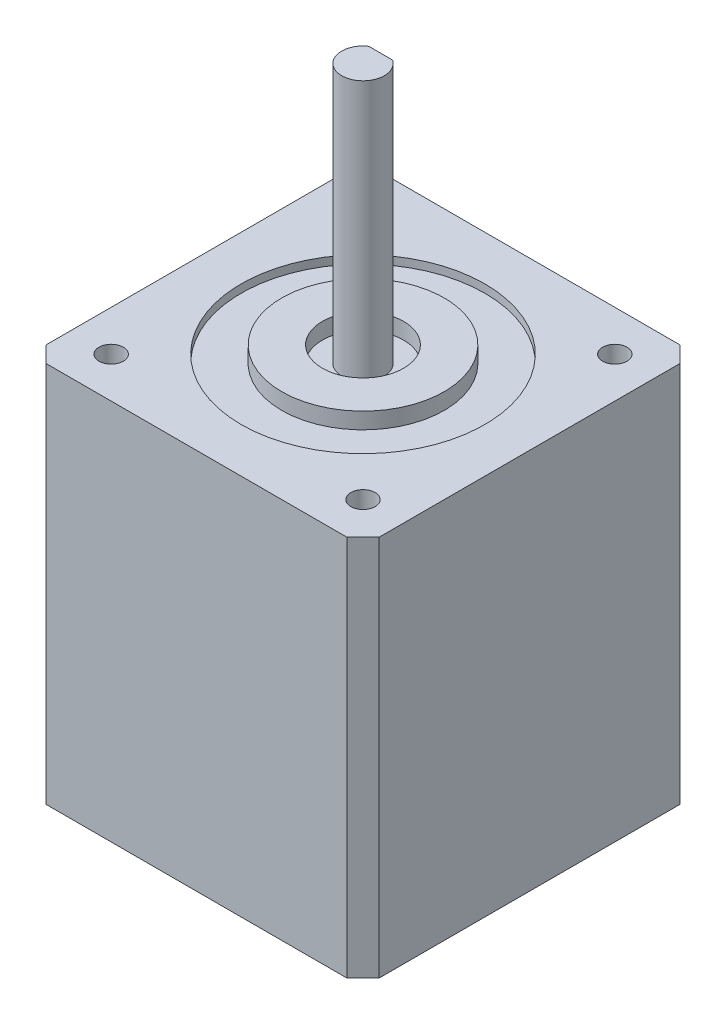
SolidWorks part; units mm, degrees
ref_plane "Front Plane" through (0, 0, 0) normal (0, 0, 1) x (1, 0, 0)
ref_plane "Top Plane" through (0, 0, 0) normal (0, 1, 0) x (1, 0, 0)
ref_plane "Right Plane" through (0, 0, 0) normal (1, 0, 0) x (0, 0, -1)
sketch "Sketch1" plane through (0, 0, 0) normal (0, 1, 0) x (1, 0, 0)
  line L0 (-20.5, 18.5) -> (-18.5, 20.5)
  line L1 (-18.5, -20.5) -> (18.5, -20.5)
  line L2 (-20.5, -18.5) -> (-20.5, 18.5)
  line L3 (-18.5, 20.5) -> (18.5, 20.5)
  line L4 (20.5, -18.5) -> (20.5, 18.5)
  line L5 (-20.5, -20.5) -> (20.5, 20.5) construction
  line L6 (-20.5, 20.5) -> (20.5, -20.5) construction
  line L7 (-18.5, -20.5) -> (-20.5, -18.5)
  line L8 (18.5, -20.5) -> (20.5, -18.5)
  line L9 (20.5, 18.5) -> (18.5, 20.5)
  point P0 (0, 0)
  dimension "D1" = 41
  dimension "D2" = 41
extrude "Boss-Extrude1" add sketch "Sketch1" along normal blind 47
sketch "Sketch2" plane through (0, 47, 0) normal (0, 1, 0) x (-1, 0, 0)
  circle A0 centre (0, 0) radius 15
extrude "Cut-Extrude1" cut sketch "Sketch2" against normal blind 1
sketch "Sketch3" plane through (0, 46, 0) normal (0, 1, 0) x (1, 0, 0)
  circle A0 centre (0, 0) radius 10
  circle A1 centre (0, 0) radius 5
extrude "Boss-Extrude2" add sketch "Sketch3" along normal blind 2
sketch "Sketch4" plane through (0, 46, 0) normal (0, 1, 0) x (1, 0, 0)
  line L0 (-1.471, 2.1754) -> (1.471, 2.1754)
  arc A0 (-1.471, 2.1754) -> (1.471, 2.1754) centre (0, 0) ccw
extrude "Boss-Extrude3" add sketch "Sketch4" along normal blind 32
hole_wizard "Ø3.0 (3) Diameter Hole1" positions "Sketch6" profile "Sketch5" hole size "Ø3.0" standard "Ansi Metric"
sketch "Sketch6" plane through (0, 47, 0) normal (0, 1, 0) x (-1, 0, 0)
  arc A0 (1.471, -2.1754) -> (-1.471, -2.1754) centre (0, 0) ccw construction
  point P0 (-15.5, -15.5)
  point P1 (15.5, -15.5)
  point P3 (15.5, 15.5)
  point P5 (-15.5, 15.5)
  dimension "D3" = 15.5
  dimension "D1" = 31
  dimension "D2" = 31
  dimension "D4" = 15.5
sketch "Sketch5" plane through (15.5, 47, -15.5) normal (1, 0, 0) x (0, 0, 1)
  line L0 (0, 0) -> (0, 5.9013)
  line L1 (0, 5.9013) -> (1.5, 5)
  line L2 (1.5, 5) -> (1.5, 0)
  line L5 (1.5, 0) -> (0, 0)
  line L10 (0, 5.9013) -> (-1.5, 5) construction
  line L11 (0, -6.35) -> (0, 107.95) construction
  dimension "Hole Dia." = 3
  dimension "Hole Depth" = 5
  dimension "Drill Angle" = 118
ref_axis "Motor Axis" through (0, 78, 0) along (0, -1, 0)
